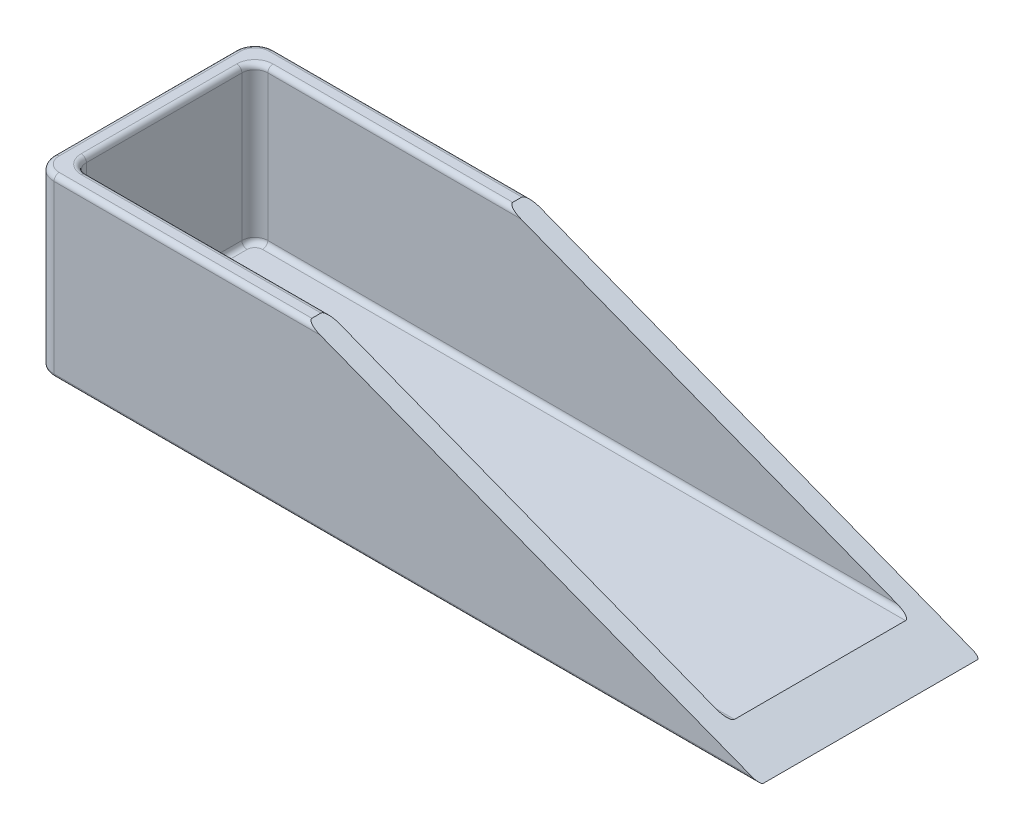
SolidWorks part; units mm, degrees
material "NEOPRENE"
ref_plane "Front" through (0, 0, 0) normal (0, 0, 1) x (1, 0, 0)
ref_plane "Top" through (0, 0, 0) normal (0, 1, 0) x (1, 0, 0)
ref_plane "Right" through (0, 0, 0) normal (1, 0, 0) x (0, 0, -1)
sketch "Sketch1" plane through (0, 0, 0) normal (0, 1, 0) x (1, 0, 0)
  line L0 (-117.475, 0) -> (-122.2375, 0) construction
  line L1 (-122.2375, 26.9875) -> (122.2375, 26.9875)
  line L2 (-122.2375, 26.9875) -> (-122.2375, -26.9875)
  line L3 (-122.2375, -26.9875) -> (122.2375, -26.9875)
  line L4 (122.2375, 26.9875) -> (122.2375, -26.9875)
  line L5 (-122.2375, 26.9875) -> (122.2375, -26.9875) construction
  line L6 (-122.2375, -26.9875) -> (122.2375, 26.9875) construction
  line L7 (117.475, 22.225) -> (-117.475, 22.225)
  line L8 (117.475, 22.225) -> (117.475, -22.225)
  line L9 (117.475, -22.225) -> (-117.475, -22.225)
  line L10 (-117.475, 22.225) -> (-117.475, -22.225)
  line L11 (117.475, 22.225) -> (-117.475, -22.225) construction
  line L12 (117.475, -22.225) -> (-117.475, 22.225) construction
  line L13 (0, 22.225) -> (0, 26.9875) construction
  point P0 (0, 0)
  point P6 (0, 0)
  dimension "D1" = 234.95
  dimension "D2" = 44.45
  dimension "THICKNESS" = 4.7625
extrude "Boss-Extrude1" add sketch "Sketch1" along normal blind 38.1
sketch "Sketch2" plane through (0, 0, 0) normal (0, -1, 0) x (1, 0, 0)
  line L4 (122.2375, -26.9875) -> (122.2375, 26.9875)
  line L5 (122.2375, 26.9875) -> (-122.2375, 26.9875)
  line L6 (-122.2375, 26.9875) -> (-122.2375, -26.9875)
  line L7 (-122.2375, -26.9875) -> (122.2375, -26.9875)
  line L8 (122.2375, -26.9875) -> (122.2375, 26.9875)
  line L9 (122.2375, 26.9875) -> (-122.2375, 26.9875)
  line L10 (-122.2375, 26.9875) -> (-122.2375, -26.9875)
  line L11 (-122.2375, -26.9875) -> (122.2375, -26.9875)
  arc A0 (107.575, 4.25) -> (107.575, 8.45) centre (107.575, 6.35) ccw construction
  arc A1 (107.575, 8.45) -> (107.575, 4.25) centre (107.575, 6.35) ccw construction
  arc A2 (76.575, 4.25) -> (76.575, 8.45) centre (76.575, 6.35) ccw construction
  arc A3 (76.575, 8.45) -> (76.575, 4.25) centre (76.575, 6.35) ccw construction
  arc A4 (107.575, 4.25) -> (107.575, 8.45) centre (107.575, 6.35) ccw
  arc A5 (107.575, 8.45) -> (107.575, 4.25) centre (107.575, 6.35) ccw
  arc A6 (76.575, 4.25) -> (76.575, 8.45) centre (76.575, 6.35) ccw
  arc A7 (76.575, 8.45) -> (76.575, 4.25) centre (76.575, 6.35) ccw
  dimension "D1" = 0
extrude "Boss-Extrude2" add sketch "Sketch2" along normal blind 4.7625
fillet "Fillet1" radius 3.175 4 edges at (117.475, 19.05, -22.225) (117.475, 19.05, 22.225) (-117.475, 19.05, 22.225) (-117.475, 19.05, -22.225)
fillet "Fillet2" radius 4.7625 4 edges at (-122.2375, 16.6687, -26.9875) (122.2375, 16.6687, -26.9875) (122.2375, 16.6687, 26.9875) (-122.2375, 16.6687, 26.9875)
sketch "Sketch4" plane through (0, -4.7625, 0) normal (0, -1, 0) x (1, 0, 0)
  line L2 (122.2375, -22.225) -> (122.2375, 22.225) construction
  line L3 (117.475, 26.9875) -> (-117.475, 26.9875) construction
  circle A0 centre (90.4875, 4.7625) radius 12.065
  dimension "D1" = 24.13
  dimension "D3" = 22.225
  dimension "D2" = 31.75
extrude "Cut-Extrude2" cut sketch "Sketch4" against normal through all
sketch "Sketch5" plane through (0, 0, -22.225) normal (0, 0, 1) x (1, 0, 0)
  line L0 (0, 0) -> (0, 19.05) construction
  line L1 (114.3, 38.1) -> (-114.3, 38.1) construction
  line L2 (-92.075, 0) -> (92.075, 0)
  line L3 (-92.075, 0) -> (-92.075, 38.1)
  line L4 (-92.075, 38.1) -> (92.075, 38.1)
  line L5 (92.075, 0) -> (92.075, 38.1)
  line L6 (-92.075, 0) -> (92.075, 38.1) construction
  line L7 (-92.075, 38.1) -> (92.075, 0) construction
  line L8 (114.3, 0) -> (-114.3, 0) construction
  dimension "D1" = 184.15
extrude "Boss-Extrude3" [suppressed] add sketch "Sketch5" along normal blind 1.651
fillet "Fillet3" [suppressed] radius 0.381
fillet "Fillet4" radius 1.27 8 edges at (116.5451, 0, -21.2951) (117.475, 0, 0) (116.5451, 0, 21.2951) (0, 0, 22.225) (-116.5451, 0, 21.2951) (-117.475, 0, 0) (-116.5451, 0, -21.2951) (0, 0, -22.225)
fillet "Fillet5" radius 0.762 8 edges at (-120.8426, -4.7625, 25.5926) (0, -4.7625, 26.9875) (120.8426, -4.7625, 25.5926) (122.2375, -4.7625, 0) (120.8426, -4.7625, -25.5926) (0, -4.7625, -26.9875) (-120.8426, -4.7625, -25.5926) (-122.2375, -4.7625, 0)
sketch "Sketch6" [suppressed] plane through (0, -4.7625, 0) normal (0, -1, 0) x (1, 0, 0)
  circle A0 centre (76.575, 6.35) radius 2.1 construction
  circle A1 centre (76.575, 6.35) radius 2.1
  circle A2 centre (107.575, 6.35) radius 2.1 construction
  circle A3 centre (107.575, 6.35) radius 2.1
extrude "Boss-Extrude4" [suppressed] add sketch "Sketch6" against normal up to surface (4.7625 mm away) up to face at (0, 0, 0)
sketch "Sketch7" [suppressed] plane through (0, -4.7625, 0) normal (0, -1, 0) x (1, 0, 0)
  circle A0 centre (-45.2, 0.936) radius 4.445
  circle A1 centre (45, 0.936) radius 4.445
  dimension "D1" = 8.89
extrude "Cut-Extrude3" [suppressed] cut sketch "Sketch7" against normal through all
sketch "Sketch8" [suppressed] plane through (0, 38.1, 0) normal (0, 1, 0) x (1, 0, 0)
  line L25 (-156.7727, 50.8) -> (156.7727, 50.8)
  line L26 (-156.7727, 50.8) -> (-156.7727, -50.8)
  line L27 (-156.7727, -50.8) -> (156.7727, -50.8)
  line L28 (156.7727, 50.8) -> (156.7727, -50.8)
  line L29 (-156.7727, 50.8) -> (156.7727, -50.8) construction
  line L30 (-156.7727, -50.8) -> (156.7727, 50.8) construction
  point P15 (0, 0)
  dimension "D2" = 101.6
  dimension "D1" = 313.5454
extrude "Cut-Extrude4" [suppressed] cut sketch "Sketch8" against normal blind 9.525
sketch "Sketch9" [suppressed] plane through (0, 0, 0) normal (0, 1, 0) x (1, 0, 0)
  line L1 (141.011, 38.276) -> (-141.011, 38.276)
  line L2 (141.011, 38.276) -> (141.011, -38.276)
  line L3 (141.011, -38.276) -> (-141.011, -38.276)
  line L4 (-141.011, 38.276) -> (-141.011, -38.276)
  line L5 (141.011, 38.276) -> (-141.011, -38.276) construction
  line L6 (141.011, -38.276) -> (-141.011, 38.276) construction
  point P0 (0, 0)
  dimension "D1" = 76.552
  dimension "D2" = 282.022
extrude "Cut-Extrude5" [suppressed] cut sketch "Sketch9" along normal offset from surface 2.54 and the other way through all up to face at (0, 38.1, 0)
sketch "Sketch10" [suppressed] plane through (0, 0, 0) normal (0, 1, 0) x (1, 0, 0)
  line L1 (-134.0132, -36.4455) -> (134.0132, -36.4455)
  line L2 (-134.0132, -36.4455) -> (-134.0132, 36.4455)
  line L3 (-134.0132, 36.4455) -> (134.0132, 36.4455)
  line L4 (134.0132, -36.4455) -> (134.0132, 36.4455)
  line L5 (-134.0132, -36.4455) -> (134.0132, 36.4455) construction
  line L6 (-134.0132, 36.4455) -> (134.0132, -36.4455) construction
  point P0 (0, 0)
  dimension "D1" = 268.0264
  dimension "D2" = 72.8909
extrude "Cut-Extrude6" [suppressed] cut sketch "Sketch10" along normal through all
sketch "Sketch11" [suppressed] plane through (0, -2.3368, 0) normal (0, -1, 0) x (1, 0, 0)
  line L1 (-127.2014, -33.7924) -> (127.2014, -33.7924)
  line L2 (-127.2014, -33.7924) -> (-127.2014, 33.7924)
  line L3 (-127.2014, 33.7924) -> (127.2014, 33.7924)
  line L4 (127.2014, -33.7924) -> (127.2014, 33.7924)
  line L5 (-127.2014, -33.7924) -> (127.2014, 33.7924) construction
  line L6 (-127.2014, 33.7924) -> (127.2014, -33.7924) construction
  point P0 (0, 0)
  dimension "D1" = 254.4028
  dimension "D2" = 67.5847
extrude "Cut-Extrude7" [suppressed] cut sketch "Sketch11" against normal offset from surface (37.8968 mm away) 2.54 up to face at (0, 38.1, 0)
sketch "Sketch12" [suppressed] plane through (0, 0, 0) normal (0, 1, 0) x (1, 0, 0)
  line L1 (-131.4623, -33.804) -> (131.4623, -33.804)
  line L2 (-131.4623, -33.804) -> (-131.4623, 33.804)
  line L3 (-131.4623, 33.804) -> (131.4623, 33.804)
  line L4 (131.4623, -33.804) -> (131.4623, 33.804)
  line L5 (-131.4623, -33.804) -> (131.4623, 33.804) construction
  line L6 (-131.4623, 33.804) -> (131.4623, -33.804) construction
  point P0 (0, 0)
  dimension "D1" = 262.9246
  dimension "D2" = 67.6081
extrude "Cut-Extrude8" [suppressed] cut sketch "Sketch12" along normal through all
sketch "Sketch13" [suppressed] plane through (0, 0, 22.225) normal (0, 0, -1) x (-1, 0, 0)
  line L0 (64.6891, 28.575) -> (64.6891, -4.7625)
  line L1 (114.3, 28.575) -> (-114.3, 28.575) construction
  line L2 (-117.475, -4.7625) -> (117.475, -4.7625) construction
  dimension "D1" = 33.3375
fillet "Fillet6" radius 1.27 16 edges at (116.5451, 38.1, -21.2951) (117.475, 38.1, 0) (116.5451, 38.1, 21.2951) (0, 38.1, 22.225) (-116.5451, 38.1, 21.2951) (-117.475, 38.1, 0) (-116.5451, 38.1, -21.2951) (120.8426, 38.1, -25.5926) (122.2375, 38.1, 0) (120.8426, 38.1, 25.5926) (0, 38.1, 26.9875) (-120.8426, 38.1, 25.5926) (-122.2375, 38.1, 0) (-120.8426, 38.1, -25.5926) (0, 38.1, -22.225) (0, 38.1, -26.9875)
fillet "Fillet7" [suppressed] radius 1.27
fillet "Fillet8" [suppressed] radius 1.27
fillet "Fillet9" radius 0.508 3 edges at (107.575, 0, 4.25) (74.4885, 0, 6.5881) (102.4747, 0, 3.3947)
sketch "Sketch14" plane through (0, 0, -26.9875) normal (0, 0, -1) x (-1, 0, 0)
  line L0 (0, -4.7625) -> (0, 38.1) construction
  line L1 (117.475, -4.7625) -> (-117.475, -4.7625) construction
  line L2 (-117.475, 38.1) -> (117.475, 38.1) construction
  line L3 (55.5625, 38.1) -> (-55.5625, -4.7625)
  line L4 (122.2375, 36.83) -> (122.2375, -4.0005) construction
  line L5 (55.5625, 38.1) -> (122.2375, 38.1)
  line L6 (122.2375, 38.1) -> (122.2375, -4.7625)
  line L7 (122.2375, -4.7625) -> (-55.5625, -4.7625)
  point P8 (0, 16.6687)
  dimension "D1" = 177.8
sketch "Sketch15" plane through (0, 0, -26.9875) normal (0, 0, -1) x (-1, 0, 0)
  line L4 (55.5625, 38.1) -> (-55.5625, -4.7625)
  line L5 (-55.5625, -4.7625) -> (122.2375, -4.7625)
  line L6 (122.2375, -4.7625) -> (122.2375, 38.1)
  line L7 (122.2375, 38.1) -> (55.5625, 38.1)
  line L8 (55.5625, 38.1) -> (-55.5625, -4.7625)
  line L9 (-55.5625, -4.7625) -> (122.2375, -4.7625)
  line L10 (122.2375, -4.7625) -> (122.2375, 38.1)
  line L11 (122.2375, 38.1) -> (55.5625, 38.1)
  dimension "D1" = 0
extrude "Cut-Extrude9" [suppressed] cut sketch "Sketch15" against normal through all
sketch "Sketch16" plane through (0, 0, -26.9875) normal (0, 0, -1) x (-1, 0, 0)
  line L0 (55.5625, 38.1) -> (-122.2375, 38.1)
  line L1 (-122.2375, 38.1) -> (-122.2375, -4.7625)
  line L2 (-122.2375, -4.7625) -> (-55.5625, -4.7625)
  line L3 (-122.2375, -4.0005) -> (-122.2375, 36.83) construction
  line L4 (55.5625, 38.1) -> (-55.5625, -4.7625)
  line L5 (-55.5625, -4.7625) -> (122.2375, -4.7625)
  line L6 (122.2375, -4.7625) -> (122.2375, 38.1)
  line L7 (122.2375, 38.1) -> (55.5625, 38.1)
  line L8 (55.5625, 38.1) -> (-55.5625, -4.7625)
  dimension "D1" = 0
extrude "Cut-Extrude10" cut sketch "Sketch16" against normal through all
sketch "Sketch17" [suppressed] plane through (0, 0, -26.9875) normal (0, 0, -1) x (-1, 0, 0)
  line L0 (0, 28.575) -> (0, -4.7625) construction
  line L1 (-117.475, 28.575) -> (117.475, 28.575) construction
  line L2 (117.475, -4.7625) -> (-117.475, -4.7625) construction
  line L3 (-55.5625, -4.7625) -> (55.5625, 28.575)
  line L4 (-122.2375, -4.0005) -> (-122.2375, 27.305) construction
  line L5 (55.5625, 28.575) -> (122.2375, 28.575)
  line L6 (122.2375, 28.575) -> (122.2375, -4.7625)
  line L7 (122.2375, -4.7625) -> (-55.5625, -4.7625)
  line L8 (122.2375, 27.305) -> (122.2375, -4.0005) construction
  point P8 (0, 11.9063)
  dimension "D1" = 177.8
sketch "Sketch18" [suppressed] plane through (0, 0, -26.9875) normal (0, 0, -1) x (-1, 0, 0)
  line L4 (55.5625, 28.575) -> (-55.5625, -4.7625)
  line L5 (122.2375, 28.575) -> (55.5625, 28.575)
  line L6 (122.2375, -4.7625) -> (122.2375, 28.575)
  line L7 (-55.5625, -4.7625) -> (122.2375, -4.7625)
  line L8 (55.5625, 28.575) -> (-55.5625, -4.7625)
  line L9 (122.2375, 28.575) -> (55.5625, 28.575)
  line L10 (122.2375, -4.7625) -> (122.2375, 28.575)
  line L11 (-55.5625, -4.7625) -> (122.2375, -4.7625)
  dimension "D1" = 0
extrude "Cut-Extrude11" [suppressed] cut sketch "Sketch18" against normal through all
sketch "Sketch19" [suppressed] plane through (0, 0, -28.575) normal (0, 0, -1) x (-1, 0, 0)
  line L0 (-53.975, -4.7625) -> (-123.825, -4.7625)
  line L2 (-123.825, -4.7625) -> (-123.825, 28.575)
  line L3 (-123.825, 28.575) -> (53.975, 28.575)
  line L4 (53.975, 28.575) -> (-53.975, -4.7625)
  line L5 (123.825, 28.575) -> (53.975, 28.575)
  line L6 (123.825, -4.7625) -> (123.825, 28.575)
  line L7 (-53.975, -4.7625) -> (123.825, -4.7625)
  line L8 (53.975, 28.575) -> (-53.975, -4.7625)
  line L12 (-123.825, -4.0005) -> (-123.825, 27.305) construction
  dimension "D1" = 0
extrude "Cut-Extrude12" [suppressed] cut sketch "Sketch19" against normal through all and the other way blind 2.54
equation "\"D1@Boss-Extrude2\"=\"THICKNESS\""
